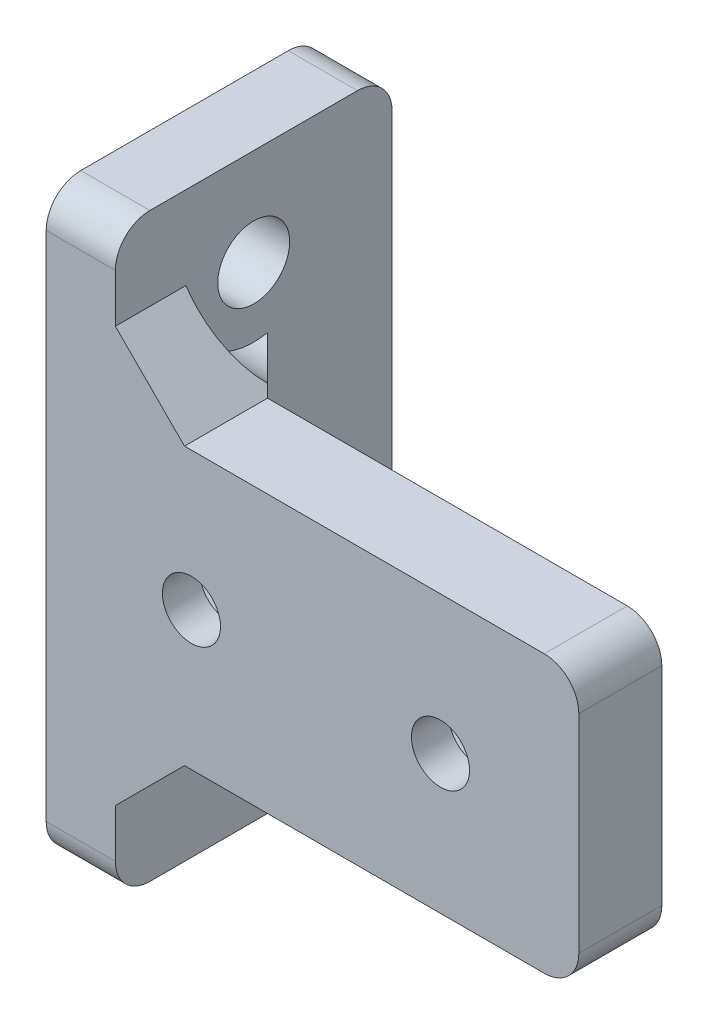
SolidWorks part; units mm, degrees
ref_plane "Спереди" through (0, 0, 0) normal (0, 0, 1) x (1, 0, 0)
ref_plane "Сверху" through (0, 0, 0) normal (0, 1, 0) x (1, 0, 0)
ref_plane "Справа" through (0, 0, 0) normal (1, 0, 0) x (0, 0, -1)
sketch "Эскиз1" plane through (0, 0, 0) normal (0, 0, 1) x (1, 0, 0)
  line L0 (-19.25, -10) -> (19.25, 10) construction
  line L1 (-19.25, 10) -> (19.25, 10)
  line L2 (-19.25, 10) -> (-19.25, -10)
  line L3 (-19.25, -10) -> (19.25, -10)
  line L4 (19.25, 10) -> (19.25, -10)
  point P4 (0, 0)
  dimension "D1" = 20
  dimension "D2" = 38.5
extrude "Бобышка-Вытянуть1" add sketch "Эскиз1" along normal blind 6
sketch "Эскиз2" plane through (-19.25, 0, 0) normal (-1, 0, 0) x (0, 0, 1)
  line L0 (6, 10) -> (6, -10) construction
  line L1 (6, 21) -> (-14, 21)
  line L2 (6, 21) -> (6, -21)
  line L3 (6, -21) -> (-14, -21)
  line L4 (-14, 21) -> (-14, -21)
  point P6 (6, 0)
  dimension "D1" = 20
  dimension "D2" = 42
extrude "Бобышка-Вытянуть2" add sketch "Эскиз2" against normal blind 5
sketch "Эскиз3" plane through (0, 0, 6) normal (0, 0, 1) x (1, 0, 0)
  line L0 (-8.75, 0) -> (9.25, 0) construction
  line L1 (-14.25, -10) -> (19.25, -10) construction
  line L2 (19.25, -10) -> (19.25, 10) construction
  line L3 (-19.25, 21) -> (-19.25, -21) construction
  circle A0 centre (9.25, 0) radius 2.1
  circle A1 centre (-8.75, 0) radius 2.1
  dimension "D1" = 4.2
  dimension "D2" = 18
  dimension "D4" = 10
  dimension "D5" = 10.5
  dimension "D3" = 10
extrude "Вырез-Вытянуть1" cut sketch "Эскиз3" against normal through all
sketch "Эскиз4" plane through (0, 0, 0) normal (0, 0, -1) x (-1, 0, 0)
  line L1 (8.75, 4.0415) -> (5.25, 2.0207)
  line L2 (5.25, 2.0207) -> (5.25, -2.0207)
  line L3 (5.25, -2.0207) -> (8.75, -4.0415)
  line L4 (8.75, -4.0415) -> (12.25, -2.0207)
  line L5 (12.25, -2.0207) -> (12.25, 2.0207)
  line L6 (12.25, 2.0207) -> (8.75, 4.0415)
  line L7 (-9.25, 4.0415) -> (-12.75, 2.0207)
  line L8 (-12.75, 2.0207) -> (-12.75, -2.0207)
  line L9 (-12.75, -2.0207) -> (-9.25, -4.0415)
  line L10 (-9.25, -4.0415) -> (-5.75, -2.0207)
  line L11 (-5.75, -2.0207) -> (-5.75, 2.0207)
  line L12 (-5.75, 2.0207) -> (-9.25, 4.0415)
  circle A0 centre (8.75, 0) radius 3.5 construction
  circle A1 centre (-9.25, 0) radius 3.5 construction
  dimension "D1" = 7
extrude "Вырез-Вытянуть2" cut sketch "Эскиз4" against normal blind 3.3
sketch "Эскиз5" plane through (-14.25, 0, 0) normal (1, 0, 0) x (0, 0, -1)
  line L0 (4, -14) -> (4, 14) construction
  line L1 (14, 21) -> (14, -21) construction
  line L2 (-6, 21) -> (14, 21) construction
  line L3 (14, -21) -> (-6, -21) construction
  circle A0 centre (4, 14) radius 2.6
  circle A1 centre (4, -14) radius 2.6
  dimension "D1" = 5.2
  dimension "D2" = 7
  dimension "D4" = 7
  dimension "D3" = 10
extrude "Вырез-Вытянуть3" cut sketch "Эскиз5" against normal through all
chamfer "Фаска2" distance 5 3 edges at (-14.25, 10, 3) (-14.25, -10, 3) (-14.25, 0, 0)
sketch "Эскиз6" plane through (-14.25, 0, 0) normal (1, 0, 0) x (0, 0, -1)
  circle A0 centre (4, -14) radius 5
  circle A1 centre (4, 14) radius 5
  dimension "D1" = 10
  dimension "D2" = 10
extrude "Вырез-Вытянуть4" cut sketch "Эскиз6" along normal through all
fillet "Скругление1" radius 2.5 6 edges at (-16.75, 21, -14) (-16.75, -21, -14) (-16.75, -21, 6) (-16.75, 21, 6) (19.25, -10, 3) (19.25, 10, 3)
